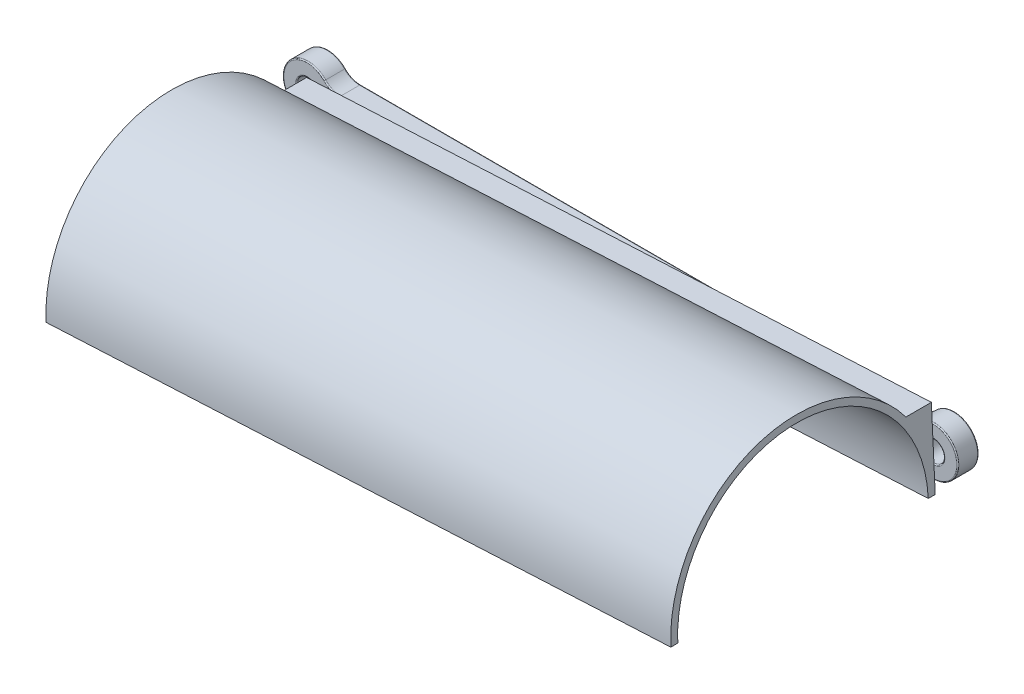
SolidWorks part; units mm, degrees
ref_plane "Front Plane" through (0, 0, 0) normal (0, 0, 1) x (1, 0, 0)
ref_plane "Top Plane" through (0, 0, 0) normal (0, 1, 0) x (1, 0, 0)
ref_plane "Right Plane" through (0, 0, 0) normal (1, 0, 0) x (0, 0, -1)
sketch "Sketch1" plane through (0, 0, 0) normal (0, 0, 1) x (1, 0, 0)
  line L0 (0, 0) -> (90, 0) construction
  line L1 (0, 3.5) -> (90, 3.5) construction
  line L2 (0, -3.5) -> (90, -3.5) construction
  line L3 (45, 0) -> (45, -3.5) construction
  line L5 (3.1623, -1.5) -> (86.8377, -1.5)
  line L6 (3.1623, -1.5) -> (3.1623, 1.5) construction
  line L7 (3.1623, 1.5) -> (86.8377, 1.5)
  line L8 (86.8377, -1.5) -> (86.8377, 1.5) construction
  line L9 (3.1623, -1.5) -> (86.8377, 1.5) construction
  line L10 (3.1623, 1.5) -> (86.8377, -1.5) construction
  arc A0 (0, 3.5) -> (0, -3.5) centre (0, 0) ccw construction
  arc A1 (90, -3.5) -> (90, 3.5) centre (90, 0) ccw construction
  circle A2 centre (0, 0) radius 3.5
  circle A3 centre (0, 0) radius 1.5
  circle A4 centre (90, 0) radius 1.5
  circle A5 centre (90, 0) radius 3.5
  point P3 (45, 0)
  dimension "D3" = 3
  dimension "D1" = 7
  dimension "D2" = 90
  dimension "D4" = 3
extrude "Boss-Extrude1" add sketch "Sketch1" along normal mid plane 3 contours A2 A3 | L5 A5 L7 A2 | A5 A4 region at (45, 0, 0) region at (-3.401, 0, 0) region at (86.599, 0, 0)
fillet "Fillet1" radius 3 4 edges at (3.1623, -1.5, 0) (86.8377, -1.5, 0) (86.8377, 1.5, 0) (3.1623, 1.5, 0)
fillet "Fillet2" radius 0.15 20 edges at (91.5, 0, -1.5) (1.5, 0, -1.5) (3.5137, -1.7404, -1.5) (45, -1.5, -1.5) (86.4863, -1.7404, -1.5) (93.5, 0, -1.5) (86.4863, 1.7404, -1.5) (45, 1.5, -1.5) (3.5137, 1.7404, -1.5) (-3.5, 0, -1.5) (91.5, 0, 1.5) (1.5, 0, 1.5) (86.4863, 1.7404, 1.5) (93.5, 0, 1.5) (86.4863, -1.7404, 1.5) (45, -1.5, 1.5) (3.5137, -1.7404, 1.5) (-3.5, 0, 1.5) (3.5137, 1.7404, 1.5) (45, 1.5, 1.5)
sketch "草图1" plane through (0, 0, 1.5) normal (0, 0, 1) x (1, 0, 0)
  circle A0 centre (10.164, 0) radius 0.3972
sketch "草图2" plane through (0, 0, 1.5) normal (0, 0, 1) x (1, 0, 0)
  line L0 (0, 0) -> (90, 0)
  line L1 (0, 0) -> (0.4828, -9.698)
  line L2 (0.4828, -9.698) -> (90.2602, -5.234)
  circle A0 centre (0, 0) radius 9.71
  circle A1 centre (90, 0) radius 5.2405
ref_plane "基准面1" through (0.4822, -9.698, 0) normal (0.0497, -0.9988, 0) x (0.9988, 0.0497, 0)
ref_point "点1"
ref_plane "基准面2" through (0, 0, 0) normal (-0.9988, -0.0497, 0) x (0, 0, 1)
ref_plane "基准面3" through (0, 0, -1.5) normal (0, 0, -1) x (-1, 0, 0)
ref_axis "基准轴1" through (0.4822, -9.698, 15.6139) along (0, 0, -1)
ref_axis "基准轴2" through (-0.6047, 12.1608, -1.5) along (0.0497, -0.9988, 0)
ref_point "点2"
sketch "草图3" plane through (0, 0, 0) normal (-0.9988, -0.0497, 0) x (0, 0, 1)
  line L0 (1.5, -9.71) -> (2.5, -9.71)
  line L6 (15.6139, -9.71) -> (-4.0036, -9.71) construction
  line L7 (-9.8088, -9.71) -> (9.8088, -9.71) construction
  line L8 (38.5, -9.71) -> (39.5, -9.71)
  line L9 (1.5, -9.71) -> (1.5, 0)
  line L10 (1.5, 0) -> (1.5, 1.5)
  line L11 (1.5, 1.5) -> (5.1593, 1.5)
  arc A2 (39.5, -9.71) -> (5.1593, 1.5) centre (20.5, -9.71) ccw
  arc A3 (38.5, -9.71) -> (2.5, -9.71) centre (20.5, -9.71) ccw
  dimension "D1" = 1.5
ref_point "点3"
ref_plane "基准面4" through (89.778, 4.464, 0) normal (-0.9988, -0.0497, 0) x (0, 0, 1)
extrude "凸台-拉伸1" add sketch "草图3" against normal up to surface (89.889 mm away) up to plane "基准面4"
